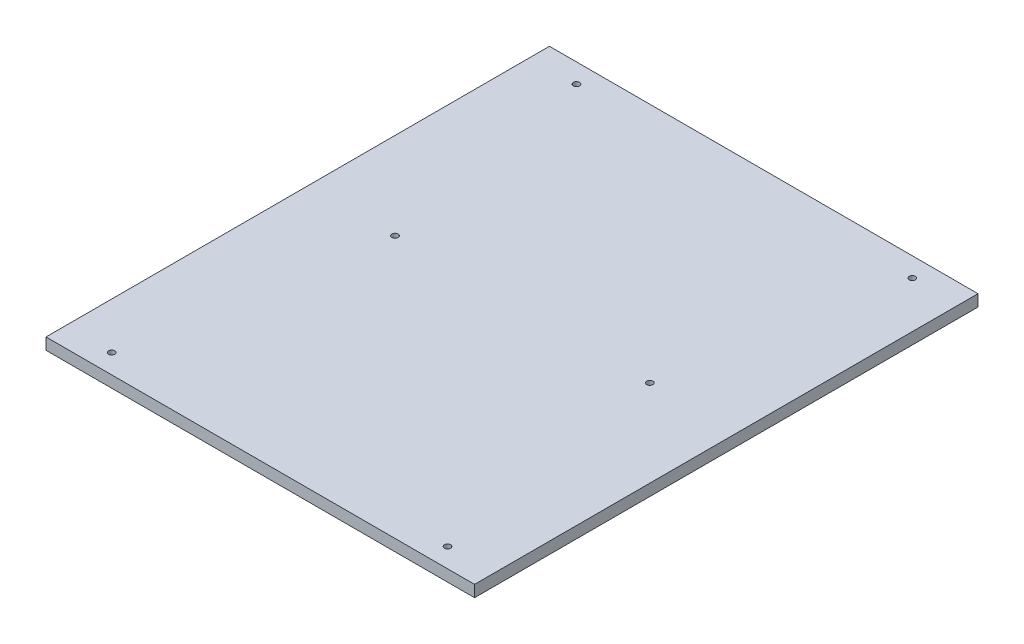
SolidWorks part; units mm, degrees
ref_plane "Front Plane" through (0, 0, 0) normal (0, 0, 1) x (1, 0, 0)
ref_plane "Top Plane" through (0, 0, 0) normal (0, 1, 0) x (1, 0, 0)
ref_plane "Right Plane" through (0, 0, 0) normal (1, 0, 0) x (0, 0, -1)
sketch "Sketch1" plane through (0, 0, 0) normal (0, 1, 0) x (1, 0, 0)
  line L0 (-111, 125.6127) -> (111, 125.6127)
  line L1 (-111, 125.6127) -> (-111, -125.6127)
  line L3 (111, 125.6127) -> (111, -125.6127)
  line L4 (-111, 125.6127) -> (111, -125.6127) construction
  line L5 (-111, -125.6127) -> (111, 125.6127) construction
  line L8 (-111, -125.6127) -> (-111, -165.6127)
  line L9 (-111, -165.6127) -> (111, -165.6127)
  line L10 (111, -125.6127) -> (111, -165.6127)
  point P7 (106.8994, -125.6127)
  point P10 (0, 0)
  dimension "D1" = 222
  dimension "D2" = 40
extrude "Boss-Extrude1" add sketch "Sketch1" along normal blind 6
sketch "Sketch2" plane through (0, 6, 0) normal (0, 1, 0) x (1, 0, 0)
  circle A0 centre (-57, 100.5142) radius 1.6
sketch "Sketch3" plane through (0, 0, 0) normal (0, -1, 0) x (1, 0, 0)
  line L0 (-111, -125.6127) -> (-111, 165.6127) construction
  line L1 (111, -125.6127) -> (-111, -125.6127)
  line L2 (111, -125.6127) -> (111, -95.1873)
  line L3 (111, -95.1873) -> (-111, -95.1873)
  line L4 (-111, -125.6127) -> (-111, -95.1873)
  circle A0 centre (66, 29.8127) radius 1.6
  circle A1 centre (-66, 29.8127) radius 1.6
  dimension "D1" = 3.2
extrude "Cut-Extrude1" cut sketch "Sketch3" against normal blind 10
sketch "Sketch4" plane through (0, 0, 0) normal (0, -1, 0) x (1, 0, 0)
  circle A0 centre (87, 155.6127) radius 1.6
  circle A1 centre (-87, 155.6127) radius 1.6
  circle A2 centre (87, -85.1873) radius 1.6
  circle A3 centre (-87, -85.1873) radius 1.6
extrude "Cut-Extrude2" cut sketch "Sketch4" against normal blind 10
